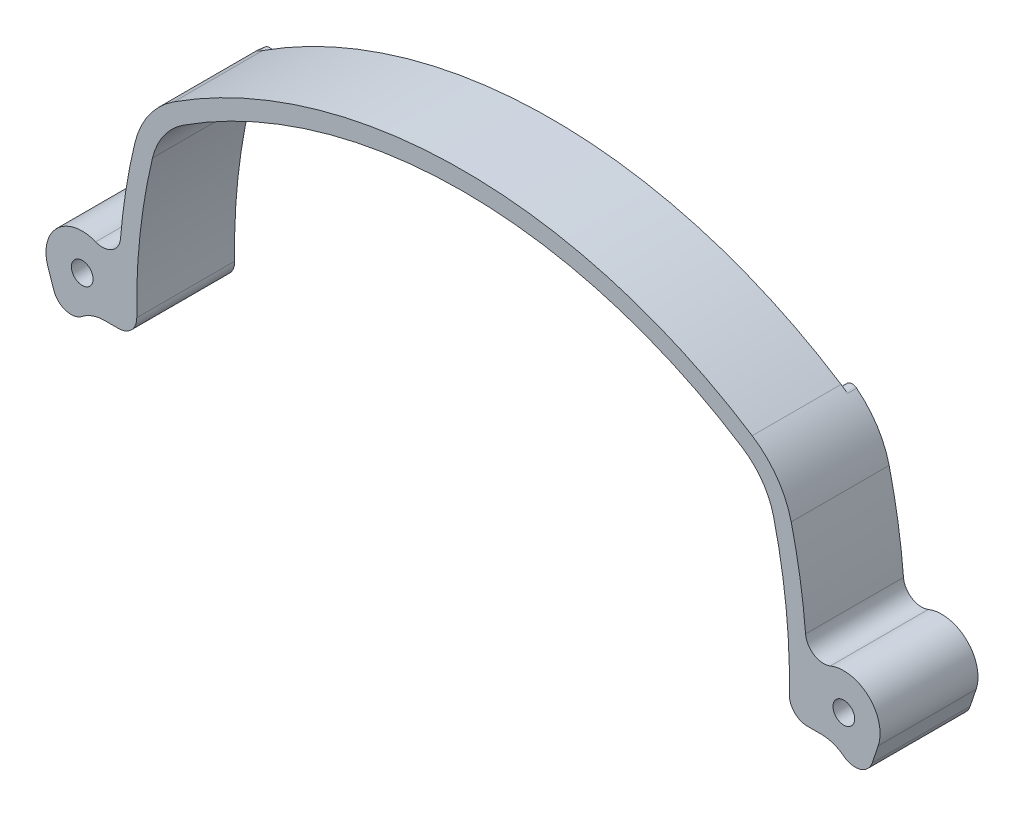
SolidWorks part; units mm, degrees
material "ABS"
ref_plane "Front Plane" through (0, 0, 0) normal (0, 0, 1) x (1, 0, 0)
ref_plane "Top Plane" through (0, 0, 0) normal (0, 1, 0) x (1, 0, 0)
ref_plane "Right Plane" through (0, 0, 0) normal (1, 0, 0) x (0, 0, -1)
sketch "Sketch1" plane through (0, 0, 0) normal (0, 0, 1) x (1, 0, 0)
  line L0 (44.45, -44.9072) -> (-44.45, -44.9072) construction
  line L1 (0, -28.5519) -> (0, 49971.4481) construction
  line L3 (-60.325, -44.9072) -> (-57.15, -44.9072)
  line L4 (57.15, -44.9072) -> (60.325, -44.9072)
  arc A0 (48.9116, -13.6057) -> (-48.9116, -13.6057) centre (0, -89.3572) ccw
  arc A1 (-54.3759, -21.3275) -> (-57.15, -44.9072) centre (44.45, -44.9072) ccw
  arc A5 (57.15, -44.9072) -> (54.3759, -21.3275) centre (-44.45, -44.9072) ccw
  arc A6 (48.9116, -13.6057) -> (54.3759, -21.3275) centre (42.0227, -24.275) cw
  arc A7 (-48.9116, -13.6057) -> (-54.3759, -21.3275) centre (-42.0227, -24.275) ccw
  arc A8 (-57.4642, -20.5906) -> (-60.325, -44.9072) centre (44.45, -44.9072) ccw
  arc A9 (-50.7868, -78.3198) -> (50.7868, -78.3198) centre (0, 0) ccw construction
  arc A12 (60.325, -44.9072) -> (57.4642, -20.5906) centre (-44.45, -44.9072) ccw
  arc A13 (50.6339, -10.9384) -> (57.4642, -20.5906) centre (42.0227, -24.275) cw
  arc A14 (50.6339, -10.9384) -> (-50.6339, -10.9384) centre (0, -89.3572) ccw
  arc A15 (-50.6339, -10.9384) -> (-57.4642, -20.5906) centre (-42.0227, -24.275) ccw
  arc A18 (-54.3759, -21.3275) -> (-54.5209, -67.8705) centre (44.45, -44.9072) ccw construction
  arc A19 (-57.4642, -20.5906) -> (-57.6138, -68.5881) centre (44.45, -44.9072) ccw construction
  arc A20 (-50.7868, -78.3198) -> (-57.6138, -68.5881) centre (-42.1496, -65.0001) cw construction
  arc A21 (-49.0593, -75.6559) -> (-54.5209, -67.8705) centre (-42.1496, -65.0001) cw construction
  arc A22 (-49.0593, -75.6559) -> (49.0593, -75.6559) centre (0, 0) ccw construction
  arc A23 (49.0593, -75.6559) -> (54.5209, -67.8705) centre (42.1496, -65.0001) ccw construction
  arc A24 (50.7868, -78.3198) -> (57.6138, -68.5881) centre (42.1496, -65.0001) ccw construction
  arc A29 (54.5209, -67.8705) -> (54.3759, -21.3275) centre (-44.45, -44.9072) ccw construction
  arc A30 (57.6138, -68.5881) -> (57.4642, -20.5906) centre (-44.45, -44.9072) ccw construction
  dimension "D4" = 101.6
  dimension "D5" = 90.17
  dimension "D13" = 12.7
  dimension "D2" = 44.45
  dimension "D3" = 88.9
  dimension "D7" = 44.9072
  dimension "D6" = 3.175
extrude "Boss-Extrude1" add sketch "Sketch1" along normal blind 17.145
sketch "Sketch5" plane through (0, 0, 17.145) normal (0, 0, 1) x (1, 0, 0)
  line L0 (0, 0) -> (-62.7623, -56.5114) construction
  line L1 (0, -1.4381) -> (0, -50001.4381) construction
  line L2 (-72.6922, -46.9361) -> (-71.6487, -50.0307)
  line L3 (-57.15, -44.9072) -> (-60.325, -44.9072)
  line L5 (-62.7623, -50.1614) -> (-60.3044, -50.1614)
  arc A0 (-62.7623, -50.1614) -> (-66.6808, -51.5147) centre (-62.7623, -56.5114) ccw
  arc A1 (-60.325, -44.9072) -> (-72.6922, -46.9361) centre (-66.675, -44.9072) ccw
  arc A2 (-57.15, -44.9072) -> (-57.13, -46.9234) centre (44.45, -44.9072) ccw
  arc A3 (-54.3759, -21.3275) -> (-57.15, -44.9072) centre (44.45, -44.9072) ccw construction
  arc A4 (-71.6487, -50.0307) -> (-66.6808, -51.5147) centre (-68.6401, -49.0163) ccw
  arc A5 (-60.3044, -50.1614) -> (-57.13, -46.9234) centre (-60.3044, -46.9864) ccw
  dimension "D1" = 12.7
  dimension "D4" = 12.7
  dimension "D5" = 3.175
  dimension "D2" = 48
  dimension "D3" = 84.455
extrude "Boss-Extrude2" add sketch "Sketch5" against normal up to surface (17.145 mm away) up to face at (0, -23.3753, 0)
hole_wizard "#6 Clearance Hole3" positions "Sketch8" profile "Sketch7" hole size "#6" standard "ANSI Inch" end condition through all
sketch "Sketch8" plane through (0, 0, 0) normal (0, 0, -1) x (-1, 0, 0)
  point P0 (66.675, -44.9072)
sketch "Sketch7" plane through (-66.675, -44.9072, 0) normal (1, 0, 0) x (0, 1, 0)
  line L0 (0, 0) -> (0, 17.145)
  line L1 (0, 17.145) -> (1.8986, 17.145)
  line L2 (1.8986, 17.145) -> (1.8986, 0)
  line L5 (1.8986, 0) -> (0, 0)
  line L11 (0, -6.35) -> (0, 107.95) construction
  dimension "Thru Hole Dia." = 3.7973
  dimension "Thru Hole Depth" = 17.145
sketch "Sketch9" plane through (0, 0, 0) normal (0, 0, -1) x (-1, 0, 0)
  line L1 (69.0763, -40.7479) -> (64.2737, -40.7479)
  line L2 (64.2737, -40.7479) -> (61.8723, -44.9072)
  line L3 (61.8723, -44.9072) -> (64.2737, -49.0664)
  line L4 (64.2737, -49.0664) -> (69.0763, -49.0664)
  line L5 (69.0763, -49.0664) -> (71.4777, -44.9072)
  line L6 (71.4777, -44.9072) -> (69.0763, -40.7479)
  circle A0 centre (66.675, -44.9072) radius 4.1592 construction
  dimension "D1" = 8.3185
extrude "Cut-Extrude2" cut sketch "Sketch9" against normal blind 6.35
mirror "Mirror1" about plane through (0, 0, 0) normal (1, 0, 0) of "Cut-Extrude2", "#6 Clearance Hole3", "Boss-Extrude2"
fillet "Fillet1" radius 3.175 2 edges at (60.325, -44.9072, 8.5725) (-60.325, -44.9072, 8.5725)
sketch "Sketch10" plane through (0, 0, 0) normal (0, 0, -1) x (-1, 0, 0)
  line L0 (-50.6339, -10.9384) -> (-48.9116, -13.6057)
  line L1 (50.6339, -10.9384) -> (48.9116, -13.6057)
  arc A0 (50.6339, -10.9384) -> (-50.6339, -10.9384) centre (0, -89.3572) ccw construction
  arc A1 (48.9116, -13.6057) -> (-48.9116, -13.6057) centre (0, -89.3572) ccw construction
  arc A2 (50.6339, -10.9384) -> (-50.6339, -10.9384) centre (0, -89.3572) ccw
  arc A3 (48.9116, -13.6057) -> (-48.9116, -13.6057) centre (0, -89.3572) ccw
extrude "Cut-Extrude3" cut sketch "Sketch10" against normal blind 1.5875
fillet "Fillet2" radius 1.27 4 edges at (-48.9116, -13.6057, 0.7937) (-50.6339, -10.9384, 0.7937) (48.9116, -13.6057, 0.7938) (50.6339, -10.9384, 0.7937)
